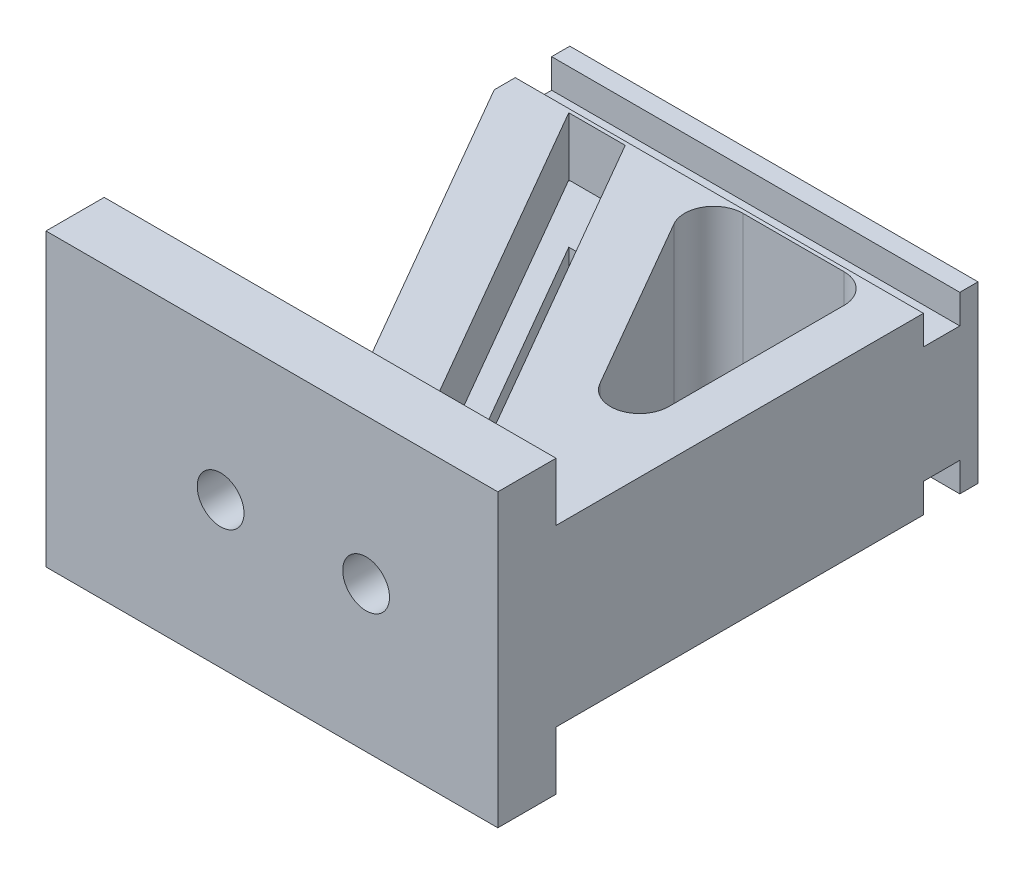
SolidWorks part; units mm, degrees
note: The reader was unsure of these and kept them because the rebuilt part matched: shared geometry of "Sketch2<3>".
other "Markup1"
sketch "Sketch15" plane through (27.5053, -19.05, 31.75) normal (0.0781, -0.0508, 0.9956) x (0.9712, 0.2293, -0.0645)
sketch "Sketch18" plane through (24.648, -15.875, 26.1937) normal (0.0781, -0.0508, 0.9956) x (0.9712, 0.2293, -0.0645)
sketch "Sketch19" plane through (24.648, -15.875, 26.1937) normal (0.0781, -0.0508, 0.9956) x (0.9712, 0.2293, -0.0645)
sketch "Sketch20" plane through (24.648, -15.875, 26.1937) normal (0.0781, -0.0508, 0.9956) x (0.9712, 0.2293, -0.0645)
material "1023 Carbon Steel Sheet (SS)"
ref_plane "Front Plane" through (0, 0, 0) normal (0, 0, 1) x (1, 0, 0)
ref_plane "Top Plane" through (0, 0, 0) normal (0, 1, 0) x (1, 0, 0)
ref_plane "Right Plane" through (0, 0, 0) normal (1, 0, 0) x (0, 0, -1)
sketch "Sketch2" plane through (0, 0, 0) normal (0, 1, 0) x (1, 0, 0)
  line L0 (-24.648, 26.1938) -> (5.598, -26.1937)
  line L1 (24.648, -26.1937) -> (-24.648, -26.1937)
  line L2 (24.648, -26.1937) -> (24.648, 26.1938)
  line L3 (24.648, 26.1938) -> (-24.648, 26.1938)
  line L4 (-24.648, -26.1937) -> (-24.648, 26.1938)
  line L5 (24.648, -26.1937) -> (-24.648, 26.1938) construction
  line L6 (24.648, 26.1938) -> (-24.648, -26.1937) construction
  line L8 (24.648, -26.1937) -> (-16.1878, -26.1937)
  line L9 (24.648, -26.1937) -> (24.648, -19.8438)
  line L12 (24.648, -26.1937) -> (-24.648, -26.1937)
  line L13 (24.648, -26.1937) -> (24.648, -19.8437)
  line L14 (24.648, -19.8437) -> (-24.648, -19.8437)
  line L15 (-24.648, -26.1937) -> (-24.648, -19.8437)
  point P0 (0, 0)
  dimension "D1" = 60
  dimension "D2" = 52.3875
  dimension "D3" = 19.05
  dimension "D4" = 6.35
extrude "Boss-Extrude1" add sketch "Sketch2" along normal mid plane 19.05 contours L2 L3 L0 L1 | L9 L8
extrude "Boss-Extrude2" add sketch "Sketch2<3>" along normal mid plane 31.75
sketch "Sketch2<3>" plane through (0, 0, 0) normal (0, 1, 0) x (1, 0, 0) same geometry as "Sketch2"
sketch "Sketch10" plane through (0, 0, -26.1938) normal (0, 0, -1) x (-1, 0, 0)
  line L0 (24.648, 9.525) -> (24.648, -9.525) construction
  line L1 (24.648, -3.175) -> (5.598, -3.175)
  line L2 (24.648, -3.175) -> (24.648, 3.175)
  line L3 (24.648, 3.175) -> (5.598, 3.175)
  line L4 (5.598, -3.175) -> (5.598, 3.175)
  line L5 (24.648, 9.525) -> (24.648, -9.525) construction
  point P6 (24.648, 0)
  point P11 (24.648, 0)
  dimension "D1" = 6.35
  dimension "D2" = 19.05
sweep "Cut-Sweep1" cut profiles "Sketch10" path edge at (-11.3581, 9.525, -3.175)
sketch "Sketch11" plane through (0, 9.525, 0) normal (0, 1, 0) x (1, 0, 0)
  line L0 (-19.8855, 26.1938) -> (-24.648, 26.1938)
  line L1 (-24.648, 26.1938) -> (-19.8855, 17.9449)
  line L2 (-24.648, 26.1938) -> (5.598, -26.1937) construction
  line L3 (-19.8855, 17.9449) -> (-19.8855, 26.1938)
  dimension "D1" = 4.7625
extrude "Cut-Extrude1" cut sketch "Sketch11" against normal through all both and the other way through all
sketch "Sketch13" plane through (0, 9.525, 0) normal (0, 1, 0) x (1, 0, 0)
  line L0 (-13.6494, 19.8438) -> (9.2641, -19.8438)
  line L1 (-7.4903, 19.8438) -> (15.4233, -19.8438)
  line L2 (-19.8855, 17.9449) -> (1.9318, -19.8437) construction
  line L5 (-13.6494, 19.8438) -> (-7.4903, 19.8438)
  line L6 (9.2641, -19.8438) -> (15.4233, -19.8438)
  line L7 (24.648, -19.8438) -> (1.9318, -19.8437) construction
  line L8 (24.648, 26.1938) -> (-19.8855, 26.1938) construction
  dimension "D1" = 5.334
  dimension "D2" = 6.35
  dimension "D3" = 6.35
extrude "Cut-Extrude2" cut sketch "Sketch13" against normal through all both
sketch "Sketch14" plane through (0, 0, 26.1937) normal (0, 0, 1) x (1, 0, 0)
  line L0 (-24.648, 0) -> (24.648, 0) construction
  line L1 (-24.648, 15.875) -> (-24.648, -15.875) construction
  line L2 (24.648, 15.875) -> (24.648, -15.875) construction
  circle A0 centre (10.277, 0) radius 2.5527
  circle A1 centre (-5.598, 0) radius 2.5527
  dimension "D1" = 5.1054
  dimension "D2" = 15.875
  dimension "D3" = 19.05
extrude "Cut-Extrude3" cut sketch "Sketch14" against normal up to next
sketch "Sketch16" plane through (0, 9.525, 0) normal (0, 1, 0) x (1, 0, 0)
  line L0 (-0.1579, 19.8438) -> (19.568, -14.3225)
  line L1 (19.568, -14.3225) -> (19.568, 19.8438)
  line L2 (19.568, 19.8438) -> (-0.1579, 19.8438)
  line L3 (15.4233, -19.8438) -> (-7.4903, 19.8438) construction
  line L4 (24.648, -19.8438) -> (24.648, 26.1938) construction
  dimension "D1" = 5.08
  dimension "D2" = 6.35
extrude "Cut-Extrude4" cut sketch "Sketch16" against normal through all
fillet "Fillet1" radius 3.175 3 edges at (19.568, 0, 14.3225) (-0.1579, 0, -19.8438) (19.568, 0, -19.8438)
sketch "Sketch17" plane through (24.648, 0, 0) normal (1, 0, 0) x (0, 0, -1)
  line L0 (-19.8438, 9.525) -> (26.1938, 9.525) construction
  line L1 (20.2406, 9.525) -> (24.2094, 9.525)
  line L2 (20.2406, 9.525) -> (20.2406, 6.35)
  line L3 (20.2406, 6.35) -> (24.2094, 6.35)
  line L4 (24.2094, 9.525) -> (24.2094, 6.35)
  line L5 (-19.8438, -9.525) -> (26.1938, -9.525) construction
  line L6 (20.2406, -9.525) -> (24.2094, -9.525)
  line L7 (20.2406, -9.525) -> (20.2406, -6.35)
  line L8 (20.2406, -6.35) -> (24.2094, -6.35)
  line L9 (24.2094, -9.525) -> (24.2094, -6.35)
  line L10 (26.1938, 9.525) -> (26.1938, -9.525) construction
  dimension "D1" = 3.9688
  dimension "D2" = 1.9844
  dimension "D3" = 3.175
extrude "Cut-Extrude5" cut sketch "Sketch17" against normal through all
